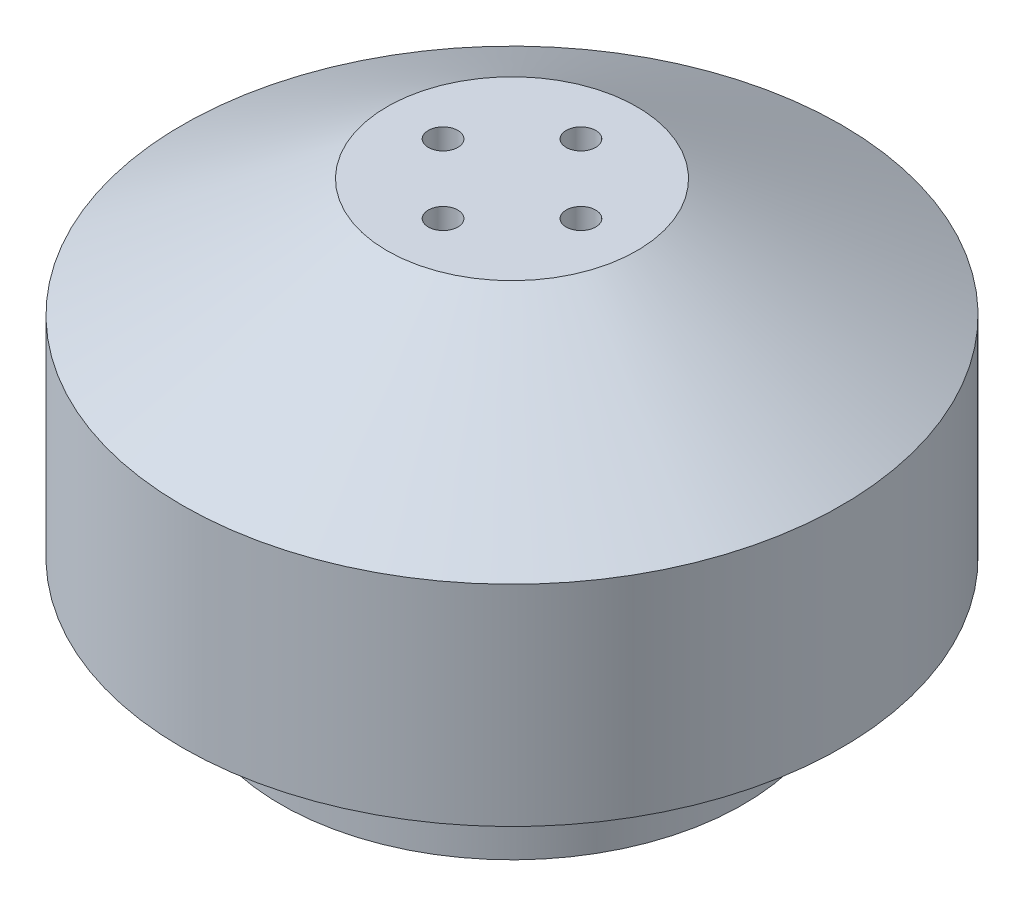
SolidWorks part; units mm, degrees
ref_plane "Front Plane" through (0, 0, 0) normal (0, 0, 1) x (1, 0, 0)
ref_plane "Top Plane" through (0, 0, 0) normal (0, 1, 0) x (1, 0, 0)
ref_plane "Right Plane" through (0, 0, 0) normal (1, 0, 0) x (0, 0, -1)
sketch "Sketch1" plane through (0, 0, 0) normal (0, 1, 0) x (1, 0, 0)
  circle A0 centre (0, 0) radius 21.25
  dimension "D1" = 42.5
extrude "Boss-Extrude1" add sketch "Sketch1" along normal blind 27.5
sketch "Sketch2" plane through (0, 0, 0) normal (0, -1, 0) x (1, 0, 0)
  circle A0 centre (0, 0) radius 14.9
  circle A2 centre (0, 0) radius 21.25
  circle A3 centre (0, 0) radius 21.25
  dimension "D1" = 0
  dimension "D2" = 6.35
extrude "Cut-Extrude1" cut sketch "Sketch2" against normal blind 6.35
chamfer "Chamfer1" distance 7.62 angle 60 1 edges at (0, 27.5, 21.25) first distance on face at (0, 27.5, 21.25)
sketch "Sketch3" plane through (0, 27.5, 0) normal (0, 1, 0) x (1, 0, 0)
  circle A0 centre (0, 4.445) radius 0.9525
  circle A1 centre (4.445, 0) radius 0.9525
  circle A2 centre (0, -4.445) radius 0.9525
  circle A3 centre (-4.445, 0) radius 0.9525
  point P12 (0, 0)
  dimension "D1" = 4.445
  dimension "D2" = 1.905
  dimension "D3" = 4
extrude "Cut-Extrude2" cut sketch "Sketch3" against normal blind 6.35
